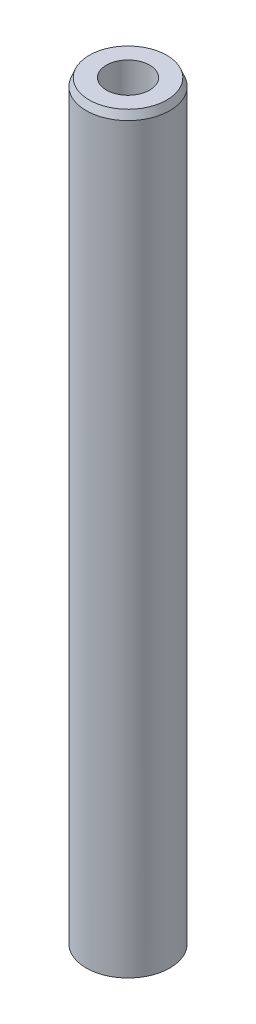
SolidWorks part; units mm, degrees
ref_plane "Front Plane" through (0, 0, 0) normal (0, 0, 1) x (1, 0, 0)
ref_plane "Top Plane" through (0, 0, 0) normal (0, 1, 0) x (1, 0, 0)
ref_plane "Right Plane" through (0, 0, 0) normal (1, 0, 0) x (0, 0, -1)
sketch "Sketch1" plane through (0, 0, 0) normal (0, 1, 0) x (1, 0, 0)
  circle A0 centre (0, 0) radius 17.5
  dimension "SHAFT_OD" = 35
extrude "Boss-Extrude1" add sketch "Sketch1" along normal blind 314.9823
sketch "Sketch2" plane through (0, 0, 0) normal (0, 1, 0) x (1, 0, 0)
  circle A0 centre (0, 0) radius 9.0531
  dimension "BORE_D" = 18.1061
extrude "Cut-Extrude1" cut sketch "Sketch2" along normal through all
chamfer "Chamfer1" distance 3.2023 angle 21.91 2 edges at (0, 314.9823, 17.5) (0, 0, 17.5) first distance on face at (0, 314.9823, 17.5) first distance on face at (0, 0, 9.0531)
